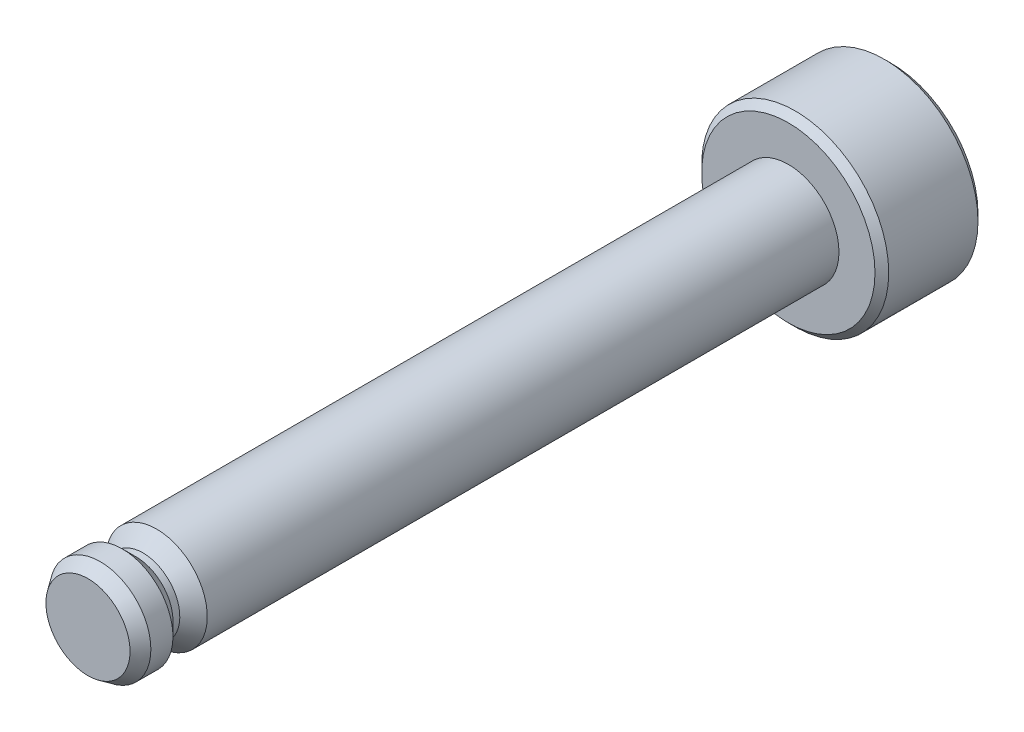
SolidWorks part; units mm, degrees
ref_plane "Front" through (0, 0, 0) normal (0, 0, 1) x (1, 0, 0)
ref_plane "Top" through (0, 0, 0) normal (0, 1, 0) x (1, 0, 0)
ref_plane "Right" through (0, 0, 0) normal (1, 0, 0) x (0, 0, -1)
sketch "Sketch2" plane through (0, 0, 0) normal (0, 0, 1) x (1, 0, 0)
  circle A0 centre (0, 0) radius 1.475
  dimension "D1" = 2.95
extrude "Shaft" add sketch "Sketch2" along normal blind 20.4
sketch "Sketch5" plane through (0, 0, 0) normal (0, 0, 1) x (1, 0, 0)
  circle A0 centre (0, 0) radius 2.725
  dimension "D1" = 5.45
extrude "Head" add sketch "Sketch5" against normal blind 3
chamfer "Chamfer1" distance 0.25 angle 55 1 edges at (1.475, 0, 20.4) first distance on face at (1.475, 0, 20.4)
chamfer "Deburs" distance 0.2 angle 45 2 edges at (2.725, 0, 0) (2.725, 0, -3)
sketch "Sketch6" plane through (0, 0, 0) normal (1, 0, 0) x (0, 0, -1)
  line L0 (0, 0) -> (-18.9, 0) construction
  line L1 (-18.9, 0) -> (-18.9, 1.075) construction
  line L2 (0, 1.475) -> (-20.043, 1.475) construction
  line L3 (-19.4, 1.475) -> (-18.4, 1.475)
  line L4 (-18.4, 1.475) -> (-18.8, 1.075)
  line L5 (-18.8, 1.075) -> (-19, 1.075)
  line L6 (-19, 1.075) -> (-19.4, 1.475)
  line L7 (-18.9, 1.075) -> (-18.9, 1.475) construction
  dimension "D1" = 18.9
  dimension "D2" = 0.4
  dimension "D3" = 1
revolve "e-Clip Notch Long" cut sketch "Sketch6" angle 360 about L0
equation "\"D1@Sketch2\"=\"Plastic Hardware OD@Box Assy.Assembly\""
equation "\"D1@Sketch5\"=\"Hardware Head Countersink Diameter@Box Assy.Assembly\"-.3mm"
equation "\"D1@Head\"=\"Countersink Depth@Box Assy.Assembly\""
equation "\"Length\"= 20mm"
equation "\"D1@Shaft\"=\"Length\"+.4mm"
equation "\"D1@Sketch6\"=\"Length\"-1.1mm"
